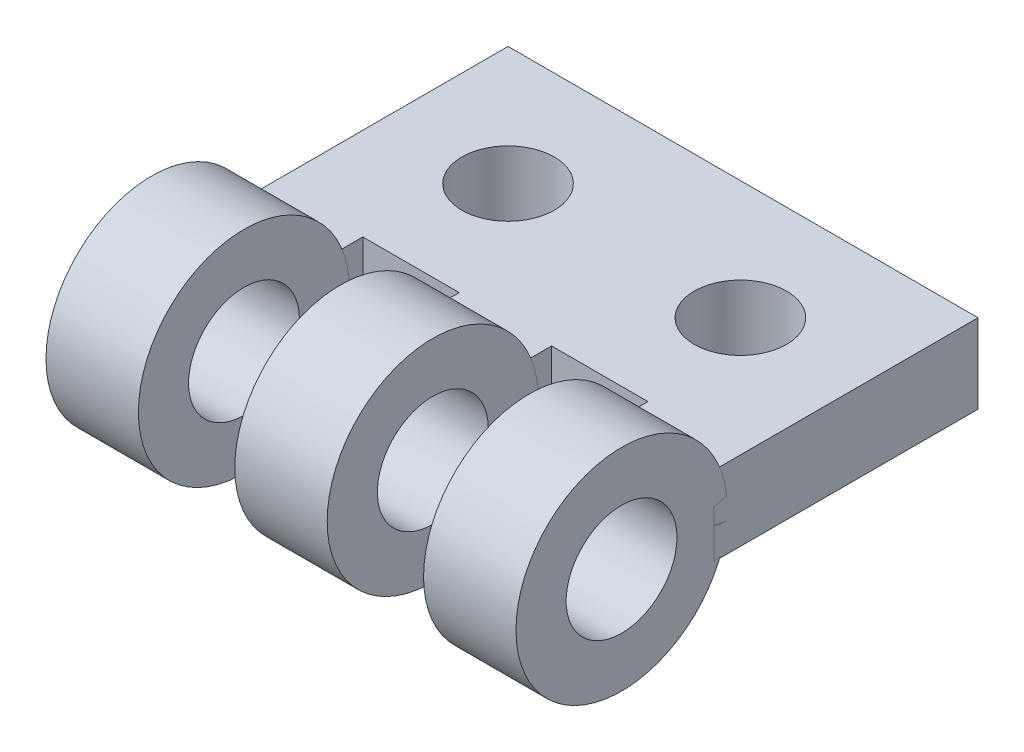
SolidWorks part; units mm, degrees
material "Acrílico (Impacto medio-alto)"
ref_plane "Alzado" through (0, 0, 0) normal (0, 0, 1) x (1, 0, 0)
ref_plane "Planta" through (0, 0, 0) normal (0, 1, 0) x (1, 0, 0)
ref_plane "Vista lateral" through (0, 0, 0) normal (1, 0, 0) x (0, 0, -1)
sketch "Croquis1" plane through (0, 0, 0) normal (1, 0, 0) x (0, -1, 0)
  circle A0 centre (0, 0) radius 4
  circle A1 centre (0, 0) radius 2.1
  dimension "D1" = 4.2
  dimension "D2" = 8
extrude "Saliente-Extruir1" add sketch "Croquis1" along normal blind 3.5
ref_axis "Eje1" through (3.5, 0, 0) along (-1, 0, 0)
pattern_linear "MatrizL3" count 3 spacing 7.15 along (-1, 0, 0) of bodies 101
ref_plane "Plano1" through (0, 0, -3.5) normal (0, 0, 1) x (1, 0, 0)
ref_plane "Plano2" through (-5.4, 0, 0) normal (1, 0, 0) x (0, 0, -1)
sketch "Croquis4" plane through (0, 0, -3.5) normal (0, 0, 1) x (1, 0, 0)
  line L0 (-5.4, -4.4) -> (-5.4, 4.4) construction
  line L1 (-14.3, 1.5) -> (3.5, 1.5)
  line L2 (-14.3, 1.5) -> (-14.3, -1.5)
  line L3 (-14.3, -1.5) -> (3.5, -1.5)
  line L4 (3.5, 1.5) -> (3.5, -1.5)
  line L5 (-14.3, 4) -> (-14.3, -4) construction
  line L6 (3.5, -4) -> (3.5, 4) construction
  point P4 (-14.3, 0)
  point P6 (-5.4, 1.5)
  dimension "D1" = 3
extrude "Saliente-Extruir2" add sketch "Croquis4" against normal blind 10 separate body
sketch "Croquis5" plane through (0, 1.5, 0) normal (0, 1, 0) x (1, 0, 0)
  line L1 (3.5, 13.5) -> (-14.3, 13.5) construction
  line L2 (3.5, 13.5) -> (3.5, 3.5) construction
  line L3 (-5.4, 13.5) -> (-5.4, 13.9354) construction
  circle A0 centre (-1, 9) radius 1.75
  circle A1 centre (-9.8, 9) radius 1.75
  dimension "D2" = 3.5
  dimension "D1" = 4.5
  dimension "D3" = 4.5
extrude "Cortar-Extruir1" cut sketch "Croquis5" against normal through all
sketch "Croquis7" plane through (0, 0, 0) normal (-1, 0, 0) x (0, 0, 1)
  line L0 (-4.5, 5.1094) -> (-4.5, -5.1094)
  line L1 (-4.5, 5.1094) -> (4.5098, 5.1094)
  line L2 (4.5098, 5.1094) -> (4.5098, -5.1094)
  line L3 (4.5098, -5.1094) -> (-4.5, -5.1094)
  circle A0 centre (0, 0) radius 4.5 construction
  point P6 (-4.5, 0)
  dimension "D1" = 9
extrude "Cortar-Extruir2" cut sketch "Croquis7" along normal up to surface (3.65 mm away) up to face at (-3.65, 0, -4)
ref_plane "Plano3" [suppressed] through (-5.4, 0, 0) normal (-1, 0, 0) x (0, 0, 1)
sketch "Croquis8" plane through (-7.15, 0, 0) normal (-1, 0, 0) x (0, 0, 1)
  line L0 (-4.5, 5.2414) -> (-4.5, -5.2414)
  line L1 (-4.5, 5.2414) -> (4.4483, 5.2414)
  line L2 (4.4483, 5.2414) -> (4.4483, -5.2414)
  line L3 (4.4483, -5.2414) -> (-4.5, -5.2414)
  circle A0 centre (0, 0) radius 4.5 construction
  point P6 (-4.5, 0)
  dimension "D1" = 9
extrude "Cortar-Extruir3" cut sketch "Croquis8" along normal up to surface (3.65 mm away) up to face at (-10.8, 0, -4)
